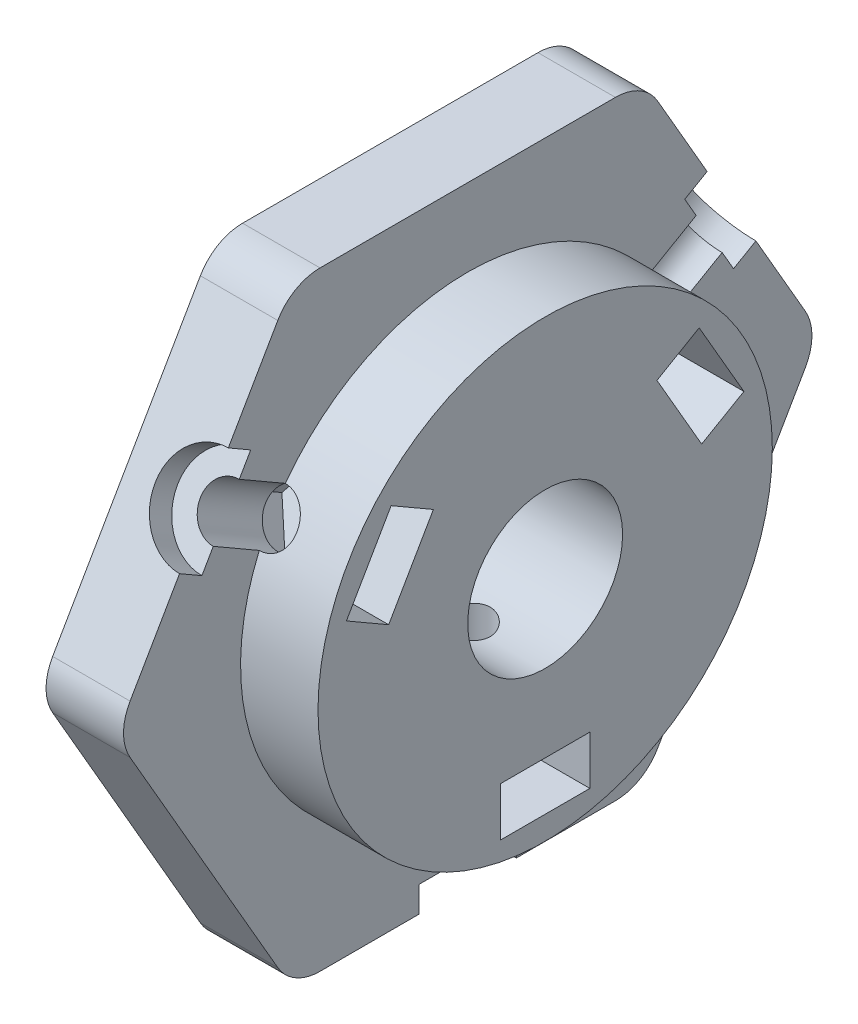
SolidWorks part; units mm, degrees
ref_plane "Front Plane" through (0, 0, 0) normal (0, 0, 1) x (1, 0, 0)
ref_plane "Top Plane" through (0, 0, 0) normal (0, 1, 0) x (1, 0, 0)
ref_plane "Right Plane" through (0, 0, 0) normal (1, 0, 0) x (0, 0, -1)
sketch "Sketch1" plane through (0, 0, 0) normal (1, 0, 0) x (0, 0, -1)
  line L1 (-10.8152, 18.7325) -> (-21.6304, 0)
  line L2 (-21.6304, 0) -> (-10.8152, -18.7325)
  line L3 (-10.8152, -18.7325) -> (10.8152, -18.7325)
  line L4 (10.8152, -18.7325) -> (21.6304, 0)
  line L5 (21.6304, 0) -> (10.8152, 18.7325)
  line L6 (10.8152, 18.7325) -> (-10.8152, 18.7325)
  circle A0 centre (0, 0) radius 18.7325 construction
  dimension "D1" = 37.465
extrude "Boss-Extrude1" add sketch "Sketch1" along normal blind 4.7625
sketch "Sketch2" plane through (4.7625, 0, 0) normal (1, 0, 0) x (0, 0, -1)
  circle A0 centre (0, 0) radius 13.97
  dimension "D1" = 27.94
extrude "Boss-Extrude2" add sketch "Sketch2" along normal blind 4.7625
sketch "Sketch3" plane through (0, -18.7325, 0) normal (0, -1, 0) x (1, 0, 0)
  line L0 (4.7625, 10.8152) -> (4.7625, -10.8152) construction
  circle A0 centre (4.7625, 0) radius 3
  dimension "D1" = 6
extrude "Cut-Extrude1" cut sketch "Sketch3" against normal blind 1.5875
ref_axis "Axis1" through (9.525, 0, 0) along (-1, 0, 0)
ref_plane "Plane1" through (0, 0, 0) normal (0, -1, 0) x (-1, 0, 0)
sketch "Sketch6" plane through (0, 0, 0) normal (0, -1, 0) x (-1, 0, 0)
  line L0 (-6.3502, 2.75) -> (-9.525, 2.75)
  line L1 (-7.9379, 0) -> (-6.3502, -2.75) construction
  line L2 (-6.3502, -2.75) -> (-3.1748, -2.75)
  line L3 (-3.1748, -2.75) -> (-1.5871, 0)
  line L4 (-1.5871, 0) -> (-3.1748, 2.75)
  line L5 (-3.1748, 2.75) -> (-6.3502, 2.75)
  line L6 (-6.3502, 2.75) -> (-7.9379, 0) construction
  line L7 (-9.525, 13.97) -> (-9.525, -13.97) construction
  line L8 (-9.525, 2.75) -> (-9.525, -2.75)
  line L9 (-9.525, -2.75) -> (-6.3502, -2.75)
  circle A0 centre (-4.7625, 0) radius 2.75 construction
  arc A3 (-4.7625, -3) -> (-4.7625, 3) centre (-4.7625, 0) ccw construction
  dimension "D1" = 5.5
extrude "Cut-Extrude4" cut sketch "Sketch6" along normal blind 3 from offset 9.525
sketch "Sketch4" plane through (0, -17.145, 0) normal (0, -1, 0) x (1, 0, 0)
  line L0 (4.7625, 3) -> (4.7625, -3) construction
  circle A0 centre (4.7625, 0) radius 1.6
  dimension "D1" = 3.2
extrude "Cut-Extrude2" cut sketch "Sketch4" against normal up to surface (7.62 mm away) up to face at (5.3973, -9.525, 0)
sketch "Sketch5" plane through (0, -17.145, 0) normal (0, -1, 0) x (1, 0, 0)
  circle A0 centre (4.7625, 0) radius 1.375
  dimension "D1" = 2.75
extrude "Cut-Extrude3" cut sketch "Sketch5" against normal blind 12.7
pattern_circular "CirPattern3" count 3 over 360 about axis through (9.525, 0, 0) along (-1, 0, 0) of "Cut-Extrude3", "Cut-Extrude2", "Cut-Extrude4", "Cut-Extrude1"
fillet "Fillet1" radius 3 6 edges at (2.3813, 18.7325, 10.8152) (2.3813, 0, 21.6304) (2.3813, -18.7325, 10.8152) (2.3813, 18.7325, -10.8152) (2.3813, 0, -21.6304) (2.3813, -18.7325, -10.8152)
sketch "Sketch7" plane through (9.525, 0, 0) normal (1, 0, 0) x (0, 0, -1)
  circle A0 centre (0, 0) radius 4.7625
  dimension "D1" = 9.525
extrude "3/8in Round" cut sketch "Sketch7" against normal through all
